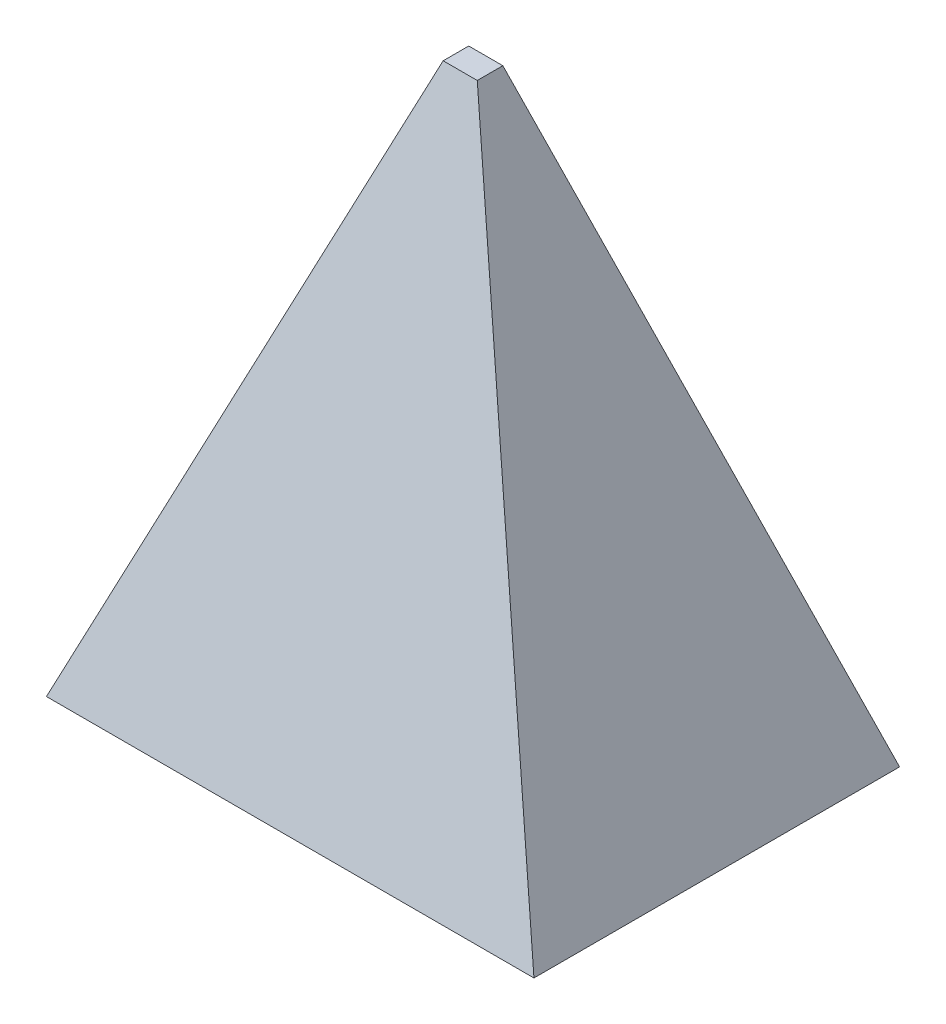
SolidWorks part; units mm, degrees
ref_plane "Front Plane" through (0, 0, 0) normal (0, 0, 1) x (1, 0, 0)
ref_plane "Top Plane" through (0, 0, 0) normal (0, 1, 0) x (1, 0, 0)
ref_plane "Right Plane" through (0, 0, 0) normal (1, 0, 0) x (0, 0, -1)
sketch "Sketch1" plane through (0, 0, 0) normal (0, 1, 0) x (1, 0, 0)
  line L1 (-50.8, -38.1) -> (50.8, -38.1)
  line L2 (-50.8, -38.1) -> (-50.8, 38.1)
  line L3 (-50.8, 38.1) -> (50.8, 38.1)
  line L4 (50.8, -38.1) -> (50.8, 38.1)
  line L5 (-50.8, -38.1) -> (50.8, 38.1) construction
  line L6 (-50.8, 38.1) -> (50.8, -38.1) construction
  point P0 (0, 0)
ref_plane "distance of measure" through (0, 120.65, 0) normal (0, 1, 0) x (1, 0, 0)
sketch "Sketch2" plane through (0, 120.65, 0) normal (0, 1, 0) x (1, 0, 0)
  line L0 (-50.8, -38.1) -> (50.8, 38.1) construction
  line L1 (-3.5535, -2.6651) -> (3.5535, -2.6651)
  line L2 (-3.5535, -2.6651) -> (-3.5535, 2.6651)
  line L3 (-3.5535, 2.6651) -> (3.5535, 2.6651)
  line L4 (3.5535, -2.6651) -> (3.5535, 2.6651)
  line L5 (-3.5535, -2.6651) -> (3.5535, 2.6651) construction
  line L6 (-3.5535, 2.6651) -> (3.5535, -2.6651) construction
  point P0 (0, 0)
loft "FOV" add profiles "Sketch1", "Sketch2" connector at (-50.8, 0, 38.1) connector at (-3.5535, 120.65, 2.6651)
